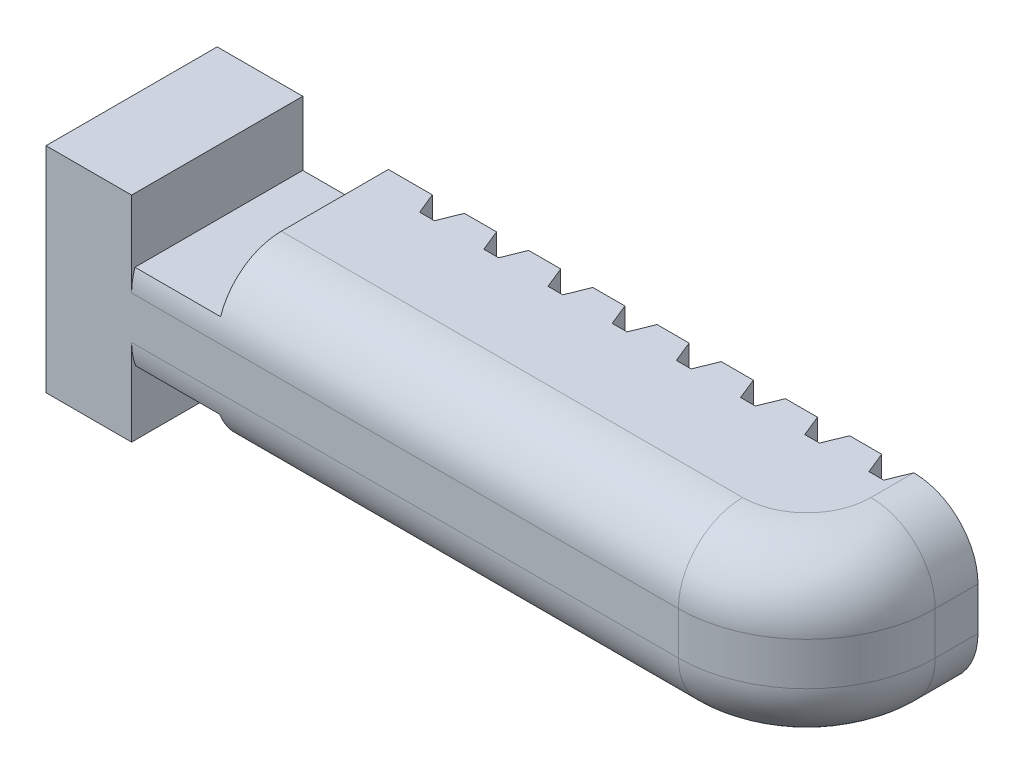
SolidWorks part; units mm, degrees
ref_plane "Front" through (0, 0, 0) normal (0, 0, 1) x (1, 0, 0)
ref_plane "Top" through (0, 0, 0) normal (0, 1, 0) x (1, 0, 0)
ref_plane "Right" through (0, 0, 0) normal (1, 0, 0) x (0, 0, -1)
sketch "Sketch1" plane through (0, 0, 0) normal (0, 0, 1) x (1, 0, 0)
  line L0 (0, 41.5205) -> (0, -58.4746)
  line L1 (0, -58.4746) -> (40, -58.4746)
  line L2 (40, -58.4746) -> (40, -28.4746)
  line L3 (40, -28.4746) -> (79.3706, -28.4746)
  line L5 (80, 11.5205) -> (40, 11.5205)
  line L6 (40, 11.5205) -> (40, 41.5205)
  line L7 (40, 41.5205) -> (0, 41.5205)
  line L9 (355.5616, 11.5254) -> (355.5616, -28.4746)
  line L11 (80, 11.5205) -> (80, 31.91)
  line L12 (80, 31.91) -> (355.5616, 31.91)
  line L13 (355.5616, 31.91) -> (355.5616, 11.5254)
  line L14 (79.3706, -28.4746) -> (79.3706, -48.09)
  line L15 (79.3706, -48.09) -> (355.5616, -48.09)
  line L16 (355.5616, -48.09) -> (355.5616, -28.4746)
  dimension "D1" = 30
  dimension "D2" = 30
  dimension "D3" = 40
  dimension "D4" = 40
  dimension "D5" = 40
  dimension "D6" = 40
  dimension "D7" = 80
extrude "Boss-Extrude1" add sketch "Sketch1" along normal mid plane 80
fillet "Fillet1" radius 60 1 edges at (355.5616, -8.09, 40)
fillet "Fillet2" radius 30 6 edges at (355.5616, -48.09, -30) (337.988, -48.09, 22.4264) (355.5616, 31.91, -30) (337.988, 31.91, 22.4264) (187.4661, -48.09, 40) (187.7808, 31.91, 40)
sketch "Sketch2" plane through (0, 0, 0) normal (0, 1, 0) x (1, 0, 0)
  line L0 (0, -40) -> (0, 40) construction
  point P0 (0, 0)
sketch "Sketch3" plane through (0, 0, -40) normal (0, 0, -1) x (-1, 0, 0)
  line L1 (-325.5616, 45.9098) -> (-310.5616, 45.9098)
  line L2 (-325.5616, 45.9098) -> (-325.5616, -64.0129)
  line L3 (-325.5616, -64.0129) -> (-310.5616, -64.0129)
  line L4 (-310.5616, 45.9098) -> (-310.5616, -64.0129)
  line L5 (-295.5616, 45.9098) -> (-295.5616, -64.0129)
  line L6 (-295.5616, 45.9098) -> (-280.5616, 45.9098)
  line L7 (-280.5616, 45.9098) -> (-280.5616, -64.0129)
  line L8 (-295.5616, -64.0129) -> (-280.5616, -64.0129)
  line L9 (-265.5616, 45.9098) -> (-265.5616, -64.0129)
  line L10 (-265.5616, 45.9098) -> (-250.5616, 45.9098)
  line L11 (-250.5616, 45.9098) -> (-250.5616, -64.0129)
  line L12 (-265.5616, -64.0129) -> (-250.5616, -64.0129)
  line L13 (-235.5616, 45.9098) -> (-235.5616, -64.0129)
  line L14 (-235.5616, 45.9098) -> (-220.5616, 45.9098)
  line L15 (-220.5616, 45.9098) -> (-220.5616, -64.0129)
  line L16 (-235.5616, -64.0129) -> (-220.5616, -64.0129)
  line L17 (-205.5616, 45.9098) -> (-205.5616, -64.0129)
  line L18 (-205.5616, 45.9098) -> (-190.5616, 45.9098)
  line L19 (-190.5616, 45.9098) -> (-190.5616, -64.0129)
  line L20 (-205.5616, -64.0129) -> (-190.5616, -64.0129)
  line L21 (-175.5616, 45.9098) -> (-175.5616, -64.0129)
  line L22 (-175.5616, 45.9098) -> (-160.5616, 45.9098)
  line L23 (-160.5616, 45.9098) -> (-160.5616, -64.0129)
  line L24 (-175.5616, -64.0129) -> (-160.5616, -64.0129)
  line L25 (-145.5616, 45.9098) -> (-145.5616, -64.0129)
  line L26 (-145.5616, 45.9098) -> (-130.5616, 45.9098)
  line L27 (-130.5616, 45.9098) -> (-130.5616, -64.0129)
  line L28 (-145.5616, -64.0129) -> (-130.5616, -64.0129)
  line L29 (-115.5616, 45.9098) -> (-115.5616, -64.0129)
  line L30 (-115.5616, 45.9098) -> (-100.5616, 45.9098)
  line L31 (-100.5616, 45.9098) -> (-100.5616, -64.0129)
  line L32 (-115.5616, -64.0129) -> (-100.5616, -64.0129)
  dimension "D1" = 15
  dimension "D2" = 8
extrude "Cut-Extrude1" cut sketch "Sketch3" against normal blind 10 draft 22
